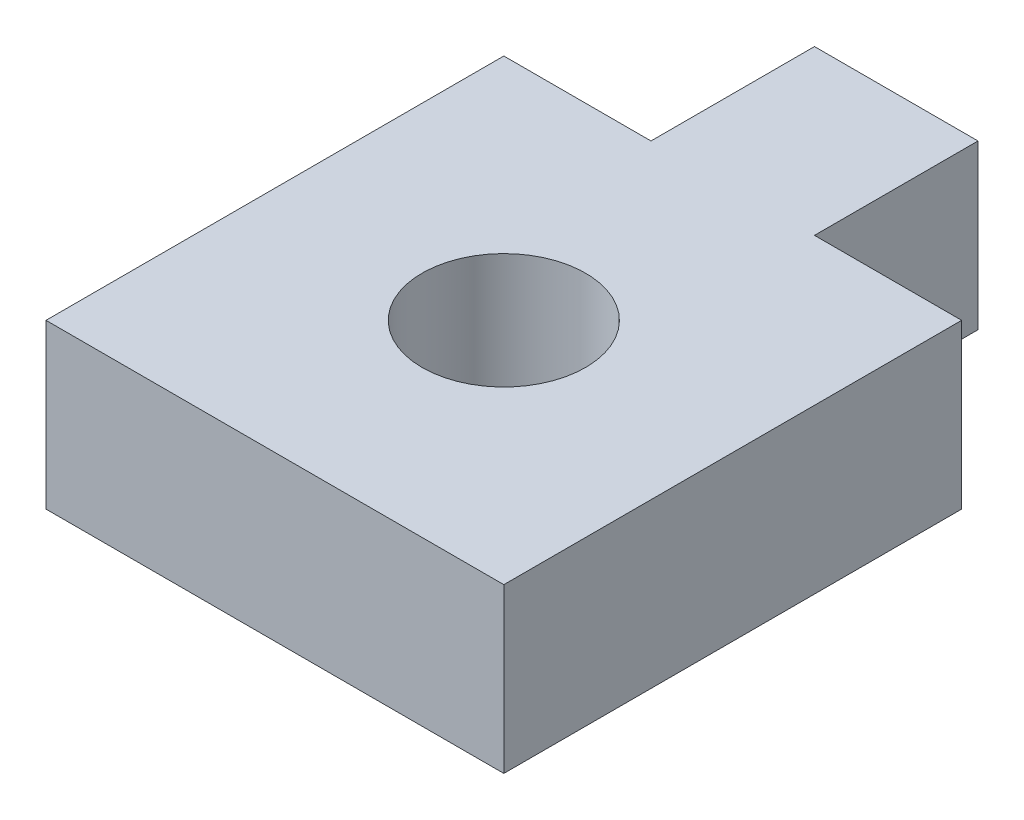
SolidWorks part; units mm, degrees
material "Balsa"
ref_plane "Front Plane" through (0, 0, 0) normal (0, 0, 1) x (1, 0, 0)
ref_plane "Top Plane" through (0, 0, 0) normal (0, 1, 0) x (1, 0, 0)
ref_plane "Right Plane" through (0, 0, 0) normal (1, 0, 0) x (0, 0, -1)
sketch "Sketch1" plane through (0, 0, 0) normal (0, 1, 0) x (1, 0, 0)
  line L0 (0, 0) -> (0, 17.78)
  line L1 (0, 17.78) -> (-5.715, 17.78)
  line L2 (-5.715, 17.78) -> (-5.715, 24.13)
  line L3 (-5.715, 24.13) -> (-12.065, 24.13)
  line L4 (-12.065, 24.13) -> (-12.065, 17.78)
  line L5 (-12.065, 17.78) -> (-17.78, 17.78)
  line L6 (-17.78, 17.78) -> (-17.78, 0)
  line L7 (-17.78, 0) -> (0, 0)
  line L8 (0, 17.78) -> (-17.78, 0) construction
  circle A0 centre (-8.89, 8.89) radius 3.175
  point P11 (0, 0)
  dimension "D5" = 6.35
  dimension "D1" = 17.78
  dimension "D2" = 17.78
  dimension "D3" = 6.35
  dimension "D4" = 6.35
extrude "Boss-Extrude1" add sketch "Sketch1" along normal blind 6.35
